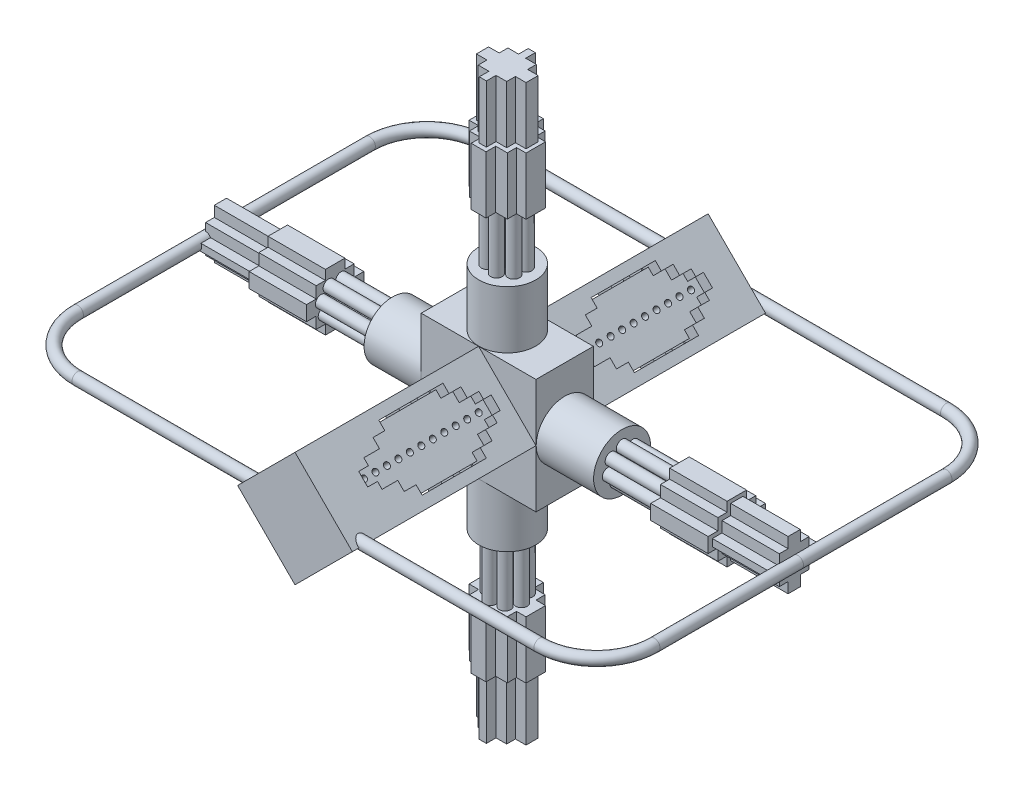
SolidWorks part; units mm, degrees
ref_plane "Front Plane" through (0, 0, 0) normal (0, 0, 1) x (1, 0, 0)
ref_plane "Top Plane" through (0, 0, 0) normal (0, 1, 0) x (1, 0, 0)
ref_plane "Right Plane" through (0, 0, 0) normal (1, 0, 0) x (0, 0, -1)
sketch "Sketch1" plane through (0, 0, 0) normal (0, 0, 1) x (1, 0, 0)
  line L0 (0, 0) -> (10, 0) construction
  line L1 (10, 0) -> (0, 10)
  line L2 (0, 10) -> (-10, 0)
  line L3 (-10, 0) -> (0, -10)
  line L4 (0, -10) -> (10, 0)
  line L5 (-10, 0) -> (0, 0) construction
  line L6 (0, 0) -> (0, 10) construction
  line L7 (0, 0) -> (0, -10) construction
  dimension "D1" = 10
  dimension "D2" = 10
  dimension "D3" = 10
  dimension "D4" = 10
extrude "Boss-Extrude2" add sketch "Sketch1" along normal blind 30
sketch "Sketch2" plane through (0, 0, 0) normal (0, 0, -1) x (-1, 0, 0)
  line L1 (-10, -10) -> (10, -10)
  line L2 (-10, -10) -> (-10, 10)
  line L3 (-10, 10) -> (10, 10)
  line L4 (10, -10) -> (10, 10)
  line L5 (-10, -10) -> (10, 10) construction
  line L6 (-10, 10) -> (10, -10) construction
  point P0 (0, 0)
  dimension "D1" = 20
  dimension "D2" = 20
extrude "Boss-Extrude3" add sketch "Sketch2" along normal blind 10
pattern_linear "LPattern1" count 2 spacing 40 along (0, 0, -1) of "Boss-Extrude2"
sketch "Sketch3" plane through (10, 0, 0) normal (1, 0, 0) x (0, 0, -1)
  line L0 (0, 0) -> (10, 0) construction
  circle A0 centre (5, 0) radius 4.963
extrude "Boss-Extrude4" add sketch "Sketch3" along normal blind 10
pattern_circular "CirPattern1" count 4 over 360 about axis through (0, 0, 0) along (0, 0, 1) of "Boss-Extrude4"
sketch "Sketch4" plane through (20, 0, 0) normal (1, 0, 0) x (0, 0, -1)
  line L0 (0, 0) -> (9.963, 0) construction
  line L1 (4.9815, 0) -> (5, 4.963) construction
  circle A0 centre (5, 0) radius 4.963 construction
  circle A1 centre (5, 0) radius 4.963 construction
  circle A2 centre (4.9907, 2.4815) radius 1
  circle A3 centre (6.9273, 1.5399) radius 1
  circle A4 centre (7.3987, -0.5612) radius 1
  circle A5 centre (6.0498, -2.2398) radius 1
  circle A6 centre (3.8965, -2.2317) radius 1
  circle A7 centre (2.5602, -0.5432) radius 1
  circle A8 centre (3.0472, 1.5544) radius 1
  circle A9 centre (4.9815, 0) radius 1
  point P26 (4.9815, 0)
  dimension "D1" = 2
  dimension "D3" = 2
  dimension "D2" = 7
extrude "Boss-Extrude5" add sketch "Sketch4" along normal blind 10
pattern_circular "CirPattern2" count 4 over 360 about axis through (0, 0, 0) along (0, 0, 1) of "Boss-Extrude5"
sketch "Sketch5" plane through (0, 30, 0) normal (0, 1, 0) x (1, 0, 0)
  line L0 (4.963, 5) -> (-4.963, 5) construction
  line L1 (-4.963, 3.3003) -> (-4.963, 6.6997)
  line L2 (-4.963, 6.6997) -> (-3.3003, 6.6997)
  line L3 (-3.3003, 6.6997) -> (-3.3003, 8.3039)
  line L4 (-3.3003, 8.3039) -> (-1.2903, 8.3039)
  line L5 (-1.2903, 8.3039) -> (-1.2903, 10)
  line L6 (-10, 10) -> (0, 10) construction
  line L7 (-1.2903, 10) -> (1.2903, 10)
  line L8 (0, 10) -> (0, 0) construction
  line L9 (0, 10) -> (0, 40) construction
  line L10 (4.963, 3.3003) -> (4.963, 6.6997)
  line L11 (4.963, 6.6997) -> (3.3003, 6.6997)
  line L12 (3.3003, 6.6997) -> (3.3003, 8.3039)
  line L13 (3.3003, 8.3039) -> (1.2903, 8.3039)
  line L14 (1.2903, 8.3039) -> (1.2903, 10)
  line L15 (1.2903, 1.6961) -> (1.2903, 0)
  line L16 (3.3003, 1.6961) -> (1.2903, 1.6961)
  line L17 (3.3003, 3.3003) -> (3.3003, 1.6961)
  line L18 (4.963, 3.3003) -> (3.3003, 3.3003)
  line L19 (-1.2903, 0) -> (1.2903, 0)
  line L20 (-1.2903, 1.6961) -> (-1.2903, 0)
  line L21 (-3.3003, 1.6961) -> (-1.2903, 1.6961)
  line L22 (-3.3003, 3.3003) -> (-3.3003, 1.6961)
  line L23 (-4.963, 3.3003) -> (-3.3003, 3.3003)
  circle A0 centre (0, 5) radius 4.963 construction
  point P28 (0, 5)
extrude "Boss-Extrude6" add sketch "Sketch5" along normal blind 10
pattern_circular "CirPattern3" count 4 every 90 about axis through (0, 0, 0) along (0, 0, 1) of "Boss-Extrude6"
sketch "Sketch6" plane through (0, 40, 0) normal (0, 1, 0) x (1, 0, 0)
  line L0 (-4.963, 5) -> (4.963, 5) construction
  line L1 (-4.963, 6.6997) -> (-4.963, 3.3003) construction
  line L2 (-4.3264, 3.9373) -> (-4.3264, 6.0627)
  line L3 (-4.3264, 6.0627) -> (-2.4815, 6.0627)
  line L4 (-2.4815, 6.0627) -> (-2.4815, 7.5846)
  line L5 (-2.4815, 7.5846) -> (-0.6219, 7.5846)
  line L6 (-0.6219, 7.5846) -> (-0.6219, 9.2666)
  line L7 (-0.6219, 9.2666) -> (0.6219, 9.2666)
  line L8 (0, 9.2666) -> (0, 0.7334) construction
  line L9 (4.3264, 5) -> (-4.3264, 5) construction
  line L10 (0.6219, 7.5846) -> (0.6219, 9.2666)
  line L11 (2.4815, 7.5846) -> (0.6219, 7.5846)
  line L12 (2.4815, 6.0627) -> (2.4815, 7.5846)
  line L13 (4.3264, 6.0627) -> (2.4815, 6.0627)
  line L14 (4.3264, 3.9373) -> (4.3264, 6.0627)
  line L15 (4.3264, 3.9373) -> (2.4815, 3.9373)
  line L16 (2.4815, 3.9373) -> (2.4815, 2.4154)
  line L17 (2.4815, 2.4154) -> (0.6219, 2.4154)
  line L18 (0.6219, 2.4154) -> (0.6219, 0.7334)
  line L19 (-0.6219, 0.7334) -> (0.6219, 0.7334)
  line L20 (-0.6219, 2.4154) -> (-0.6219, 0.7334)
  line L21 (-2.4815, 2.4154) -> (-0.6219, 2.4154)
  line L22 (-2.4815, 3.9373) -> (-2.4815, 2.4154)
  line L23 (-4.3264, 3.9373) -> (-2.4815, 3.9373)
  point P25 (0, 5)
extrude "Boss-Extrude7" add sketch "Sketch6" along normal blind 10
pattern_circular "CirPattern4" count 4 over 360 about axis through (0, 0, 0) along (0, 0, 1) of "Boss-Extrude7"
sketch3d "3DSketch1"
  line L0 (-50, 0.1327, -5.1327) -> (-50, 0.1327, 19.8673)
  line L1 (-0.2423, 0.1327, 29.8673) -> (-40, 0.1327, 29.8673)
  line L3 (-0.2423, 0.1327, -41.0149) -> (-40, 0.1327, -41.0149)
  line L4 (-50, 0.1327, -5.1327) -> (-50, 0.1327, -31.0149)
  line L5 (-0.2423, 0.1327, -41.0149) -> (40.4913, 0.1327, -41.0149)
  line L6 (50.4913, 0.1327, -5.1327) -> (50.4913, 0.1327, -31.0149)
  line L7 (50.4913, 0.1327, -5.1327) -> (50.4913, 0.1327, 19.8673)
  line L8 (-0.2423, 0.1327, 29.8673) -> (40.4913, 0.1327, 29.8673)
  arc A0 (-50, 0.1327, 19.8673) -> (-40, 0.1327, 29.8673) centre (-40, 0.1327, 19.8673) ccw
  arc A1 (-50, 0.1327, -31.0149) -> (-40, 0.1327, -41.0149) centre (-40, 0.1327, -31.0149) ccw
  arc A2 (50.4913, 0.1327, 19.8673) -> (40.4913, 0.1327, 29.8673) centre (40.4913, 0.1327, 19.8673) ccw
  arc A3 (50.4913, 0.1327, -31.0149) -> (40.4913, 0.1327, -41.0149) centre (40.4913, 0.1327, -31.0149) ccw
  point P5 (0, 0, 0)
  point P6 (-50, 0.1327, 29.8673)
  point P7 (-40, 10.1327, 19.8673)
  point P12 (-40, -9.8673, -31.0149)
  point P13 (-53.9122, 28.3454, -17.1377)
  point P14 (-66.2761, 6.9589, -13.0138)
  point P15 (0, 0, 0)
  point P21 (40.4913, -9.8673, 19.8673)
  point P24 (1.0376, 1.9879, 20.3013)
  point P26 (40.4913, 10.1327, -31.0149)
  point P27 (0.7066, 0.3135, -50.9745)
  dimension "D3" = 10
  dimension "D4" = 10
  dimension "D1" = 90
  dimension "D2" = 35
sweep "Sweep1" add path "3DSketch1" circular profile diameter 2 parameters "D3"=2
sketch "Sketch31" plane through (-5, 5, 0) normal (-0.7071, 0.7071, 0) x (0, 0, 1)
  line L0 (0, 0) -> (30, 0) construction
  line L1 (0, 7.0711) -> (0, -7.0711) construction
  line L2 (30, 7.0711) -> (30, -5.4818) construction
  line L3 (2.025, -1.1138) -> (2.025, 1.1138)
  line L4 (2.025, 1.1138) -> (3.365, 1.1138)
  line L5 (3.365, 1.1138) -> (3.365, 2.2477)
  line L6 (3.365, 2.2477) -> (5.3751, 2.2477)
  line L7 (5.3751, 2.2477) -> (5.3751, 3.8455)
  line L8 (5.3751, 3.8455) -> (7.4367, 3.8455)
  line L9 (7.4367, 3.8455) -> (7.4367, 5.3402)
  line L10 (7.4367, 5.3402) -> (18.621, 5.3402)
  line L11 (18.621, 5.3402) -> (18.621, 3.8455)
  line L12 (18.621, 3.8455) -> (20.6826, 3.8455)
  line L13 (20.6826, 3.8455) -> (20.6826, 2.2477)
  line L14 (20.6826, 2.2477) -> (23.4143, 2.2477)
  line L15 (23.4143, 2.2477) -> (23.4143, 1.1138)
  line L16 (23.4143, 1.1138) -> (25.1151, 1.1138)
  line L17 (25.1151, 1.1138) -> (25.1151, -1.1138)
  line L18 (25.1151, 0) -> (2.025, 0) construction
  line L19 (23.4143, -1.1138) -> (25.1151, -1.1138)
  line L20 (23.4143, -2.2477) -> (23.4143, -1.1138)
  line L21 (20.6826, -2.2477) -> (23.4143, -2.2477)
  line L22 (20.6826, -3.8455) -> (20.6826, -2.2477)
  line L23 (18.621, -3.8455) -> (20.6826, -3.8455)
  line L24 (18.621, -5.3402) -> (18.621, -3.8455)
  line L25 (7.4367, -5.3402) -> (18.621, -5.3402)
  line L26 (7.4367, -3.8455) -> (7.4367, -5.3402)
  line L27 (5.3751, -3.8455) -> (7.4367, -3.8455)
  line L28 (5.3751, -2.2477) -> (5.3751, -3.8455)
  line L29 (3.365, -2.2477) -> (5.3751, -2.2477)
  line L30 (3.365, -1.1138) -> (3.365, -2.2477)
  line L31 (2.025, -1.1138) -> (3.365, -1.1138)
extrude "Cut-Extrude1" cut sketch "Sketch31" against normal blind 2
sketch "Sketch32" plane through (-3.5858, 3.5858, 0) normal (-0.7071, 0.7071, 0) x (0, 0, 1)
  line L0 (2.025, 0) -> (25.1151, 0) construction
  line L1 (2.025, 1.1138) -> (2.025, -1.1138) construction
  line L2 (25.1151, -1.1138) -> (25.1151, 1.1138) construction
  circle A0 centre (13.57, 0) radius 0.5
  point P8 (13.57, 0)
  dimension "D1" = 1
extrude "Cut-Extrude2" cut sketch "Sketch32" against normal blind 2
pattern_linear "LPattern2" count 6 spacing 2 along (0, 0, -1) count 6 spacing 2 along (0, 0, 1) of "Cut-Extrude2"
sketch "Sketch33" plane through (0, 0, 30) normal (0, 0, 1) x (1, 0, 0)
  line L0 (0, 10) -> (-10, 0)
  line L1 (0, 10) -> (-10, 0) construction
  line L2 (-10, 0) -> (0, -10)
  line L3 (-4.963, -10) -> (4.963, -10) construction
  line L4 (0, -10) -> (10, 0)
  line L5 (10, 0) -> (0, 10)
extrude "Boss-Extrude8" add sketch "Sketch33" along normal blind 2
pattern_circular "CirPattern5" count 4 over 360 about axis through (0, 0, 0) along (0, 0, 1) of "LPattern2", "Cut-Extrude2", "Cut-Extrude1"
pattern_linear "LPattern3" count 2 spacing 37 along (0, 0, -1) of "CirPattern5", "Cut-Extrude1", "Cut-Extrude2", "LPattern2"
